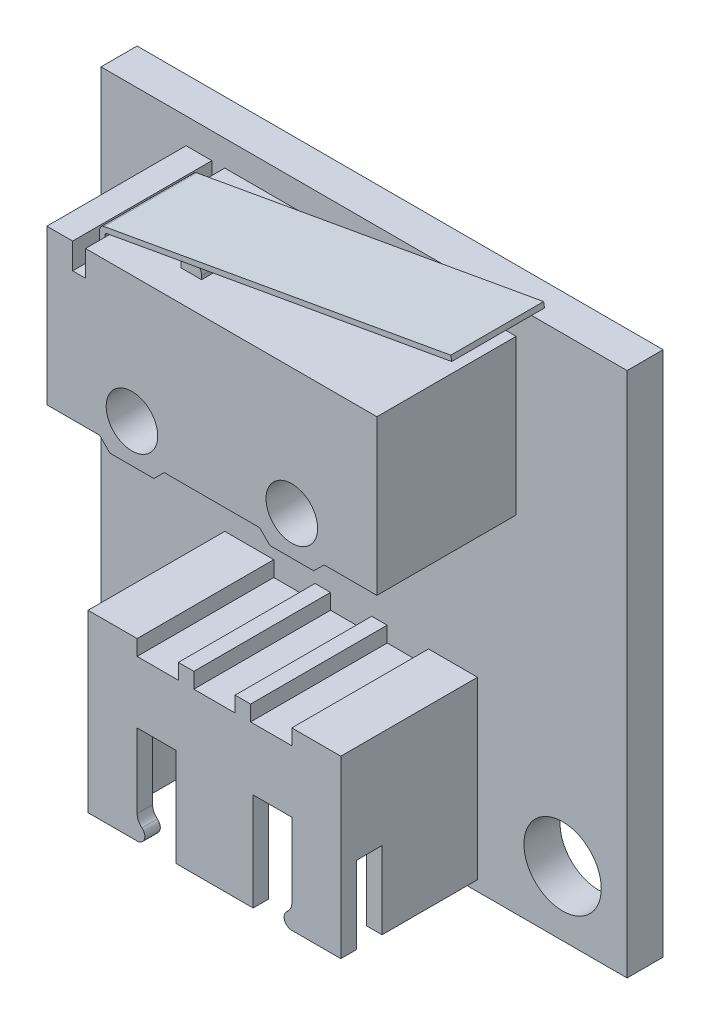
SolidWorks part; units mm, degrees
ref_plane "Спереди" through (0, 0, 0) normal (0, 0, 1) x (1, 0, 0)
ref_plane "Сверху" through (0, 0, 0) normal (0, 1, 0) x (1, 0, 0)
ref_plane "Справа" through (0, 0, 0) normal (1, 0, 0) x (0, 0, -1)
sketch "Эскиз1" plane through (0, 0, 0) normal (0, 0, 1) x (1, 0, 0)
  line L0 (0, 0) -> (20.4, 20.4) construction
  line L1 (0, 0) -> (20.4, 0)
  line L2 (0, 0) -> (0, 20.4)
  line L3 (0, 20.4) -> (20.4, 20.4)
  line L4 (20.4, 0) -> (20.4, 20.4)
  line L5 (0, 20.4) -> (20.4, 0) construction
  line L6 (4, 16.4) -> (16.4, 16.4) construction
  line L7 (4, 16.4) -> (4, 4) construction
  line L8 (4, 4) -> (16.4, 4) construction
  line L9 (16.4, 16.4) -> (16.4, 4) construction
  line L10 (4, 16.4) -> (16.4, 4) construction
  line L11 (4, 4) -> (16.4, 16.4) construction
  line L13 (1, 1) -> (19.4, 1) construction
  line L14 (1, 1) -> (1, 19.4) construction
  line L15 (1, 19.4) -> (19.4, 19.4) construction
  line L16 (19.4, 1) -> (19.4, 19.4) construction
  line L17 (1, 1) -> (19.4, 19.4) construction
  line L18 (1, 19.4) -> (19.4, 1) construction
  circle A2 centre (17.9, 2.5) radius 1.5
  circle A3 centre (2.5, 2.5) radius 1.5
  point P5 (10.2, 10.2)
  point P22 (10.2, 10.2)
  dimension "D1" = 20.4
  dimension "D2" = 20.4
  dimension "D3" = 12.4
  dimension "D4" = 18.4
extrude "Бобышка-Вытянуть1" add sketch "Эскиз1" along normal blind 1.4
sketch "Эскиз2" plane through (0, 0, 1.4) normal (0, 0, 1) x (1, 0, 0)
  line L0 (10.2, 20.4) -> (10.2, 0) construction
  line L1 (20.4, 20.4) -> (0, 20.4) construction
  line L2 (0, 0) -> (20.4, 0) construction
  line L4 (5.3, 7.7) -> (15.1, 7.7)
  line L5 (5.3, 7.7) -> (5.3, 0.9)
  line L6 (5.3, 0.9) -> (15.1, 0.9)
  line L7 (15.1, 7.7) -> (15.1, 0.9)
  line L8 (5.3, 7.7) -> (15.1, 0.9) construction
  line L9 (5.3, 0.9) -> (15.1, 7.7) construction
  point P6 (10.2, 4.3)
  dimension "D1" = 9.8
  dimension "D2" = 6.8
  dimension "D3" = 0.9
extrude "Бобышка-Вытянуть2" add sketch "Эскиз2" along normal blind 5.3 from offset 0.5
sketch "Эскиз3" plane through (0, 0.9, 0) normal (0, -1, 0) x (1, 0, 0)
  line L4 (10.2, 6.6) -> (10.2, 2.5) construction
  line L5 (15.1, 7.2) -> (15.1, 1.9) construction
  line L6 (5.3, 5.6) -> (15.1, 5.6)
  line L7 (5.3, 5.6) -> (5.3, 6.6)
  line L8 (5.9, 2.5) -> (14.5, 2.5)
  line L9 (14.5, 2.5) -> (14.5, 6.6)
  line L10 (14.5, 6.6) -> (5.9, 6.6)
  line L11 (5.9, 6.6) -> (5.9, 2.5)
  line L12 (5.9, 2.5) -> (14.5, 2.5)
  line L13 (14.5, 2.5) -> (14.5, 6.6)
  line L14 (14.5, 6.6) -> (5.9, 6.6)
  line L15 (5.9, 6.6) -> (5.9, 2.5)
  line L16 (5.3, 6.6) -> (15.1, 6.6)
  line L17 (15.1, 5.6) -> (15.1, 6.6)
  line L18 (5.3, 5.6) -> (15.1, 6.6) construction
  line L19 (5.3, 6.6) -> (15.1, 5.6) construction
  line L20 (5.3, 7.2) -> (15.1, 7.2) construction
  line L21 (11.7, 7.2) -> (13.2, 7.2)
  line L22 (11.7, 7.2) -> (11.7, 6.6)
  line L23 (11.7, 6.6) -> (13.2, 6.6)
  line L24 (13.2, 7.2) -> (13.2, 6.6)
  line L25 (7.2, 7.2) -> (7.2, 6.6)
  line L26 (8.7, 6.6) -> (7.2, 6.6)
  line L27 (8.7, 7.2) -> (8.7, 6.6)
  line L28 (8.7, 7.2) -> (7.2, 7.2)
  point P2 (10.2, 6.1)
  line M12 (15.1, 1.9) -> (15.1, 7.2)
  line M13 (15.1, 7.2) -> (5.3, 7.2)
  line M14 (5.3, 7.2) -> (5.3, 1.9)
  dimension "D2" = 1
  dimension "D3" = 1.5
  dimension "D4" = 3
  dimension "D1" = 0.6
extrude "Вырез-Вытянуть1" cut sketch "Эскиз3" against normal blind 3 contours L16 L6 L15 M14 | L16 L13 L6 M12 region at (5.6, 0.9, 6.1) region at (14.8, 0.9, 6.1)
extrude "Вырез-Вытянуть2" cut sketch "Эскиз3<3>" against normal blind 3.8 contours L27 L25 L14 M13 | L24 L22 L16 M13 region at (7.95, 0.9, 6.9) region at (12.45, 0.9, 6.9)
sketch "Эскиз3<3>" plane through (0, 0.9, 0) normal (0, -1, 0) x (1, 0, 0) same geometry as "Эскиз3"
extrude "Вырез-Вытянуть3" cut sketch "Эскиз3<4>" against normal blind 5.2 contours L6 L15 L12 L13 | L14 L16 L15 L6 L13 region at (10.2, 0.9, 6.1) region at (10.2, 0.9, 4.05)
sketch "Эскиз3<4>" plane through (0, 0.9, 0) normal (0, -1, 0) x (1, 0, 0) same geometry as "Эскиз3"
sketch "Эскиз4" plane through (0, 6.1, 0) normal (0, -1, 0) x (1, 0, 0)
  line L2 (5.3, 4.2) -> (7.2, 4.2)
  line L3 (5.8795, 4.2) -> (14.5, 4.2)
  line L4 (14.5, 2.5) -> (14.5, 6.6)
  line L5 (14.5, 6.6) -> (5.9, 6.6)
  line L6 (5.9, 6.6) -> (5.9, 2.5)
  line L7 (5.9, 2.5) -> (14.5, 2.5)
  line L8 (14.5, 2.5) -> (14.5, 6.6)
  line L9 (14.5, 6.6) -> (5.9, 6.6)
  line L10 (5.9, 6.6) -> (5.9, 2.5)
  line L11 (5.9, 2.5) -> (14.5, 2.5)
  line M6 (14.5, 2.5) -> (14.5, 6.6)
  line M8 (5.9, 6.6) -> (5.9, 2.5)
  line M9 (5.9, 2.5) -> (14.5, 2.5)
  dimension "D1" = 0
  dimension "D2" = 3
extrude "Вырез-Вытянуть4" cut sketch "Эскиз4" against normal blind 0.3 contours L3 M8 M9 M6 region at (10.2, 6.1, 3.35)
chamfer "Фаска1" distance 0.3 angle 45 1 edges at (10.2, 6.1, 4.2)
sketch "Эскиз5" plane through (0, 0, 7.2) normal (0, 0, 1) x (1, 0, 0)
  line L0 (13.2, 4.7) -> (13.2, 0.9) construction
  line L1 (7.2, 4.7) -> (7.2, 0.9) construction
  line L2 (7.5, 4.7) -> (7.5, 1.2) construction
  line L3 (8.7, 4.7) -> (7.2, 4.7) construction
  line L4 (12.9, 4.7) -> (12.9, 1.2) construction
  line L5 (13.2, 4.7) -> (11.7, 4.7) construction
  circle A0 centre (13.2, 1.2) radius 0.3
  circle A1 centre (7.2, 1.2) radius 0.3
  dimension "D1" = 5.4
extrude "Бобышка-Вытянуть3" add sketch "Эскиз5" against normal up to surface (0.6 mm away) up to face at (10.2, 3.25, 6.6)
fillet "Скругление2" radius 0.5 2 edges at (13.2, 1.5, 6.9) (7.2, 1.5, 6.9)
sketch "Эскиз6" plane through (0, 0, 7.2) normal (0, 0, 1) x (1, 0, 0)
  line L0 (10.2, 7.7) -> (10.2, 0.9) construction
  line L1 (15.1, 7.7) -> (5.3, 7.7) construction
  line L2 (8.7, 0.9) -> (11.7, 0.9) construction
  line L3 (7.2, 8.3) -> (7.2, 7.1)
  line L4 (9.4, 8.3) -> (11, 8.3)
  line L5 (9.4, 8.3) -> (9.4, 7.1)
  line L6 (9.4, 7.1) -> (11, 7.1)
  line L7 (11, 8.3) -> (11, 7.1)
  line L8 (9.4, 8.3) -> (11, 7.1) construction
  line L9 (9.4, 7.1) -> (11, 8.3) construction
  line L10 (7.2, 7.1) -> (8.8, 7.1)
  line L11 (8.8, 8.3) -> (8.8, 7.1)
  line L12 (11.6, 8.3) -> (11.6, 7.1)
  line L13 (11.6, 7.1) -> (13.2, 7.1)
  line L14 (13.2, 8.3) -> (13.2, 7.1)
  line L27 (5.3, 0.9) -> (7.2, 0.9)
  line L28 (7.2, 1.8245) -> (7.2, 4.7)
  line L29 (7.2, 4.7) -> (8.7, 4.7)
  line L30 (8.7, 4.7) -> (8.7, 0.9)
  line L31 (8.7, 0.9) -> (11.7, 0.9)
  line L32 (11.7, 0.9) -> (11.7, 4.7)
  line L33 (11.7, 4.7) -> (13.2, 4.7)
  line L34 (13.2, 4.7) -> (13.2, 1.8245)
  line L35 (13.2, 0.9) -> (15.1, 0.9)
  line L36 (15.1, 0.9) -> (15.1, 7.7)
  line L37 (15.1, 7.7) -> (5.3, 7.7)
  line L38 (5.3, 7.7) -> (5.3, 0.9)
  line L39 (5.3, 0.9) -> (7.2, 0.9)
  line L40 (7.2, 1.8245) -> (7.2, 4.7)
  line L41 (7.2, 4.7) -> (8.7, 4.7)
  line L42 (8.7, 4.7) -> (8.7, 0.9)
  line L43 (8.7, 0.9) -> (11.7, 0.9)
  line L44 (11.7, 0.9) -> (11.7, 4.7)
  line L45 (11.7, 4.7) -> (13.2, 4.7)
  line L46 (13.2, 4.7) -> (13.2, 1.8245)
  line L47 (13.2, 0.9) -> (15.1, 0.9)
  line L48 (15.1, 0.9) -> (15.1, 7.7)
  line L49 (15.1, 7.7) -> (5.3, 7.7)
  line L50 (5.3, 7.7) -> (5.3, 0.9)
  arc A4 (7.2, 0.9) -> (7.3875, 1.4342) centre (7.2, 1.2) ccw
  arc A5 (7.2, 1.8245) -> (7.3875, 1.4342) centre (7.7, 1.8245) ccw
  arc A6 (13.0125, 1.4342) -> (13.2, 1.8245) centre (12.7, 1.8245) ccw
  arc A7 (13.0125, 1.4342) -> (13.2, 0.9) centre (13.2, 1.2) ccw
  arc A8 (7.2, 0.9) -> (7.3875, 1.4342) centre (7.2, 1.2) ccw
  arc A9 (7.2, 1.8245) -> (7.3875, 1.4342) centre (7.7, 1.8245) ccw
  arc A10 (13.0125, 1.4342) -> (13.2, 1.8245) centre (12.7, 1.8245) ccw
  arc A11 (13.0125, 1.4342) -> (13.2, 0.9) centre (13.2, 1.2) ccw
  line M39 (15.1, 7.7) -> (5.3, 7.7)
  dimension "D1" = 1.6
  dimension "D2" = 0.6
  dimension "D4" = 0.6
  dimension "D6" = 0.6
  dimension "D7" = 0
  dimension "D3" = 2
  dimension "D5" = 2
extrude "Вырез-Вытянуть5" cut sketch "Эскиз6" against normal up to surface (5.3 mm away) contours L11 L3 L10 M39 | L7 L5 L6 M39 | L14 L12 L13 M39 region at (8, 7.4, 7.2) region at (10.2, 7.4, 7.2) region at (12.4, 7.4, 7.2) up to face at (10.2, 4.3, 1.9)
sketch "Эскиз7" plane through (0, 0, 1.4) normal (0, 0, 1) x (1, 0, 0)
  line L0 (10.2, 20.4) -> (10.2, 0) construction
  line L1 (20.4, 20.4) -> (0, 20.4) construction
  line L2 (0, 0) -> (20.4, 0) construction
  line L3 (7.1, 15) -> (13.3, 15) construction
  line L4 (3.8, 13.9) -> (16.6, 13.9)
  line L5 (3.8, 13.9) -> (3.8, 19.9)
  line L6 (3.8, 19.9) -> (16.6, 19.9)
  line L7 (16.6, 13.9) -> (16.6, 19.9)
  line L8 (3.8, 13.9) -> (16.6, 19.9) construction
  line L9 (3.8, 19.9) -> (16.6, 13.9) construction
  line L10 (3.8, 13.5) -> (16.6, 13.5)
  line L11 (5.85, 13.9) -> (6.25, 13.5)
  line L12 (6.25, 13.5) -> (7.1, 13.5)
  line L13 (7.1, 13.5) -> (7.1, 15) construction
  line L14 (8.35, 13.9) -> (7.95, 13.5)
  line L15 (14.55, 13.9) -> (14.15, 13.5)
  line L16 (12.05, 13.9) -> (12.45, 13.5)
  circle A0 centre (7.1, 15) radius 1
  circle A1 centre (13.3, 15) radius 1
  point P6 (10.2, 16.9)
  point P19 (10.2, 15)
  dimension "D4" = 2
  dimension "D6" = 6.2
  dimension "D1" = 0.5
  dimension "D2" = 12.8
  dimension "D3" = 6
  dimension "D5" = 4.9
  dimension "D8" = 2.5
  dimension "D9" = 45
  dimension "D7" = 0.4
extrude "Бобышка-Вытянуть4" add sketch "Эскиз7" along normal blind 5.4 from offset 0.5 separate body contours L4 L7 L6 L5 A1 A0 | L14 L4 L11 L10 | L4 L16 L10 L15 | L5 | L7 region at (10.2, 17.0693, 1.4) region at (7.1, 13.7127, 1.4) region at (13.3, 13.7127, 1.4)
sketch "Эскиз8" plane through (0, 0, 1.4) normal (0, 0, 1) x (1, 0, 0)
  circle A0 centre (13.3, 15) radius 1 construction
  circle A1 centre (7.1, 15) radius 1 construction
  circle A2 centre (13.3, 15) radius 1
  circle A3 centre (7.1, 15) radius 1
extrude "Вырез-Вытянуть6" cut sketch "Эскиз8" against normal through all
ref_plane "Плоскость1" through (0, 0, 4.6) normal (0, 0, 1) x (1, 0, 0)
sketch "Эскиз10" plane through (0, 0, 4.6) normal (0, 0, 1) x (1, 0, 0)
  line L0 (3.8, 19.9) -> (16.6, 19.9) construction
  line L1 (4.8, 19.9) -> (5.3, 19.9)
  line L2 (4.8, 19.9) -> (4.8, 18.9)
  line L3 (4.8, 18.9) -> (5.3, 18.9)
  line L4 (5.3, 19.9) -> (5.3, 18.9)
  line L5 (3.8, 13.9) -> (3.8, 19.9) construction
  dimension "D1" = 0.5
  dimension "D2" = 1
  dimension "D3" = 1
extrude "Вырез-Вытянуть9" cut sketch "Эскиз10" against normal through all both and the other way through all
sketch "Эскиз11" plane through (0, 0, 4.6) normal (0, 0, 1) x (1, 0, 0)
  line L3 (5.2324, 19.9147) -> (18.6, 22.3031)
  line L4 (18.6, 22.3031) -> (18.5648, 22.5)
  line L5 (18.5648, 22.5) -> (5.1148, 20.0969)
  line L6 (4.95, 19.05) -> (5.15, 19.05)
  line L7 (5.15, 19.05) -> (5.15, 19.9)
  line L8 (4.95, 19.9) -> (4.95, 19.05)
  line L9 (4.95, 19.05) -> (5.15, 19.05)
  line L10 (5.15, 19.05) -> (5.15, 19.8163)
  line L11 (4.95, 19.8961) -> (4.95, 19.05)
  line L12 (4.95, 19.9) -> (4.95, 19.8961)
  line L13 (16.6, 13.9) -> (16.6, 19.9) construction
  line L14 (12.45, 13.5) -> (14.15, 13.5) construction
  arc A0 (5.15, 19.8163) -> (5.2324, 19.9147) centre (5.25, 19.8163) cw
  arc A1 (5.1148, 20.0969) -> (4.95, 19.9) centre (5.15, 19.9) ccw
  dimension "D6" = 0.1
  dimension "D7" = 0.2
  dimension "D2" = 0.2
  dimension "D3" = 0.2
  dimension "D4" = 2
  dimension "D5" = 9
  dimension "D1" = 0.15
extrude "Бобышка-Вытянуть5" add sketch "Эскиз11" along normal mid plane 3.6 separate body
sketch "Эскиз12" plane through (0, 0, 4.6) normal (0, 0, 1) x (1, 0, 0)
  line L0 (8.2, 20.0386) -> (8.2, 19.4386) construction
  line L1 (8.6, 20.0386) -> (8.6, 19.4386)
  line L2 (7.8, 20.0386) -> (7.8, 19.4386)
  line L3 (5.2324, 19.9147) -> (18.6, 22.3031) construction
  line L4 (3.8, 13.9) -> (3.8, 19.9) construction
  arc A0 (8.6, 20.0386) -> (7.8, 20.0386) centre (8.2, 20.0386) ccw
  arc A1 (7.8, 19.4386) -> (8.6, 19.4386) centre (8.2, 19.4386) ccw
  point P2 (8.2, 19.7386)
  dimension "D1" = 4.8
  dimension "D2" = 0.8
  dimension "D3" = 0.6
extrude "Бобышка-Вытянуть6" add sketch "Эскиз12" along normal mid plane 3 separate body
